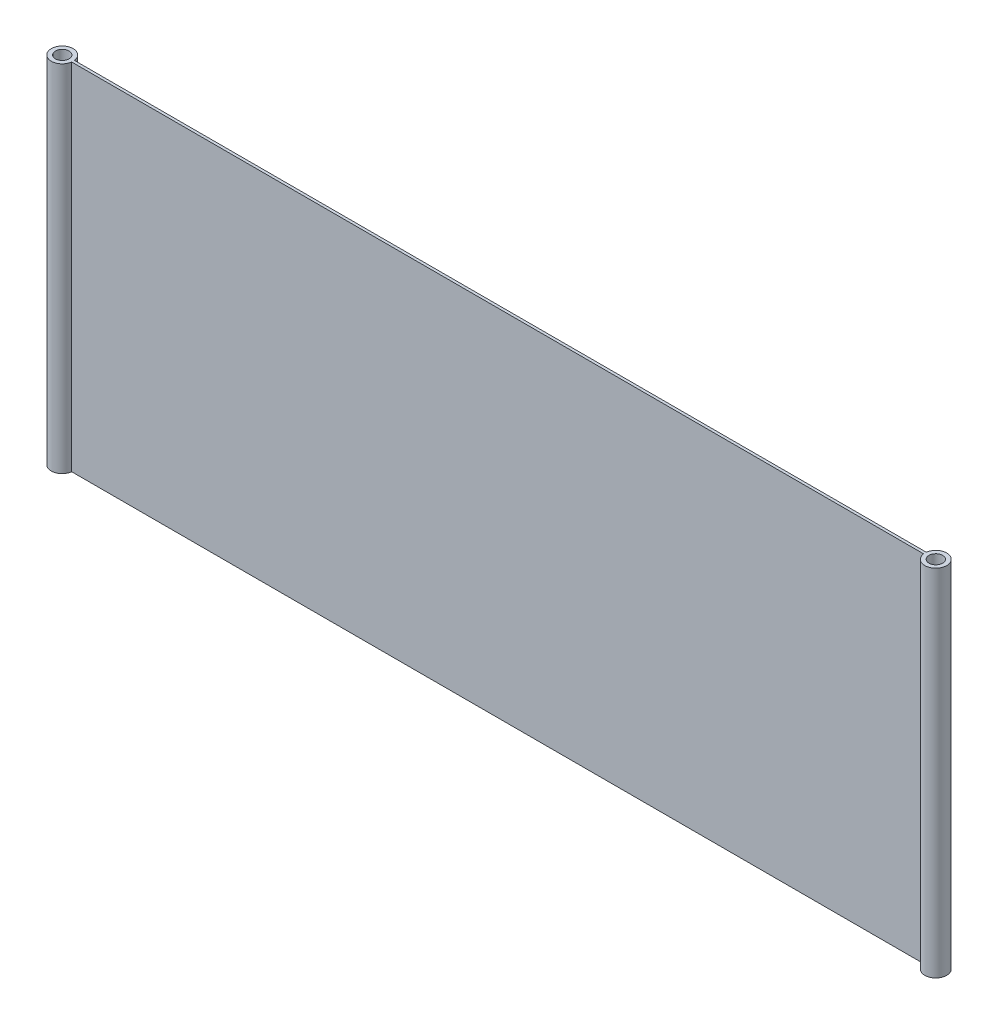
SolidWorks part; units mm, degrees
ref_plane "Alzado" through (0, 0, 0) normal (0, 0, 1) x (1, 0, 0)
ref_plane "Planta" through (0, 0, 0) normal (0, 1, 0) x (1, 0, 0)
ref_plane "Vista lateral" through (0, 0, 0) normal (1, 0, 0) x (0, 0, -1)
sketch "Croquis2" plane through (0, 0, 0) normal (0, 1, 0) x (1, 0, 0)
  line L0 (0, -0.25) -> (0, 0.25) construction
  line L3 (-78.0129, 0.25) -> (78.0129, 0.25)
  line L5 (-78.0129, -0.25) -> (78.0129, -0.25)
  arc A0 (-78.0129, 0.25) -> (-78.0129, -0.25) centre (-80, 0) ccw
  circle A1 centre (-80, 0) radius 1.25
  circle A2 centre (80, 0) radius 1.25
  arc A3 (78.0129, 0.25) -> (78.0129, -0.25) centre (80, 0) cw
  point P1 (-48.3643, 0.25)
  point P2 (-47.2066, -0.3494)
  point P4 (-47.1269, 1.9746)
  point P18 (-47.6435, -0.8041)
  point P19 (0, 0)
  point P22 (-46.4092, 0.7556)
  dimension "D1" = 2.5
  dimension "D3" = 2.0028
  dimension "D2" = 0.5
  dimension "D4" = 80
extrude "Saliente-Extruir2" add sketch "Croquis2" along normal blind 65
